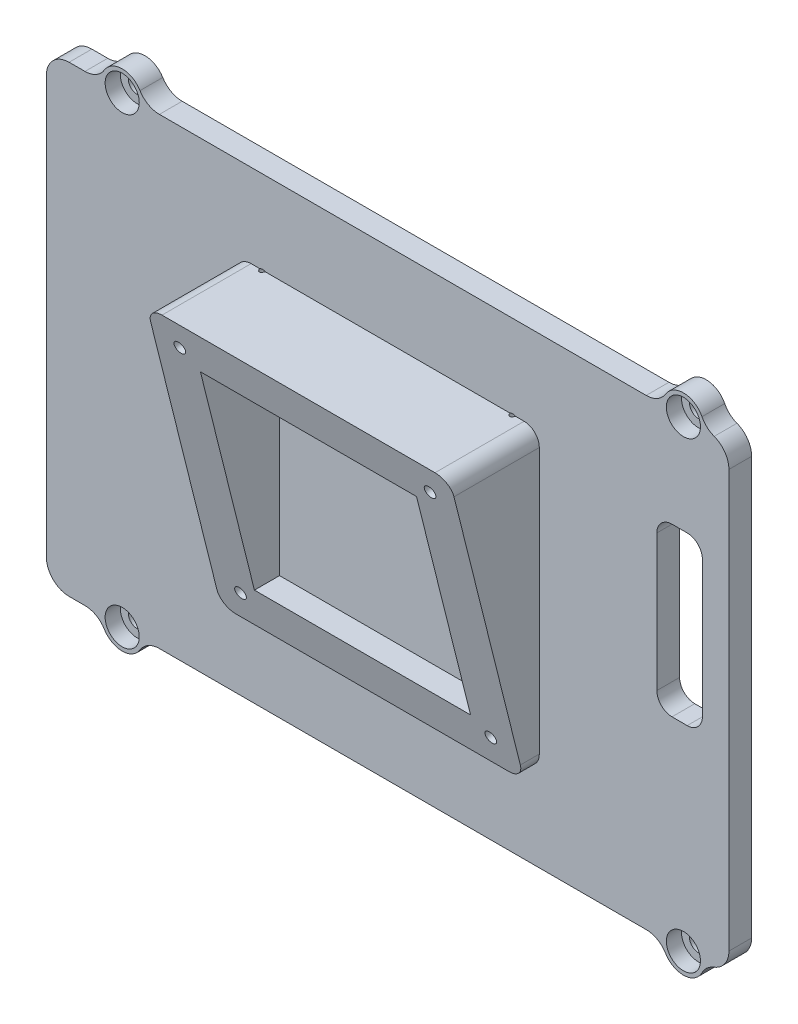
SolidWorks part; units mm, degrees
ref_plane "Спереди" through (0, 0, 0) normal (0, 0, 1) x (1, 0, 0)
ref_plane "Сверху" through (0, 0, 0) normal (0, 1, 0) x (1, 0, 0)
ref_plane "Справа" through (0, 0, 0) normal (1, 0, 0) x (0, 0, -1)
sketch "Эскиз1" plane through (0, 0, 0) normal (0, 1, 0) x (1, 0, 0)
  line L0 (0, 45) -> (0, -45) construction
  line L1 (-30.5, 45) -> (30.5, 45)
  line L2 (-30.5, 45) -> (-30.5, -45)
  line L3 (-30.5, -45) -> (30.5, -45)
  line L4 (30.5, 45) -> (30.5, -45)
  line L6 (-30.5, 0) -> (30.5, 0) construction
  point P8 (0, 0)
  dimension "D1" = 90
  dimension "D2" = 61
extrude "боковые стенки" [suppressed] add sketch "Эскиз1" along normal blind 18
sketch "Эскиз7" plane through (0, 0, 0) normal (0, 1, 0) x (1, 0, 0)
  line L1 (-30.5, 45) -> (30.5, 45)
  line L2 (-30.5, 45) -> (-30.5, -45)
  line L3 (-30.5, -45) -> (30.5, -45)
  line L4 (30.5, 45) -> (30.5, -45)
extrude "крышка" [suppressed] add sketch "Эскиз7" along normal blind 12
dome "Купол6" [suppressed] faces to dome 1 distance 10 parameters "D1"=10
shell "Оболочка1" [suppressed] thickness 2
sketch "Эскиз11" [suppressed] plane through (-30.5, 0, 0) normal (-1, 0, 0) x (0, 0, 1)
  line L1 (-45, 30) -> (45, 30) construction
  line L2 (0, 30) -> (45, 30)
  line L4 (45, 30) -> (45, 18)
  ellipse E0 centre (0, 18) end of major axis (-45, 18) minor radius 12 (45, 18) -> (0, 30) ccw
  dimension "D1" = 12
extrude "скругление вдоль" [suppressed] cut sketch "Эскиз11" against normal through all
sketch "Эскиз12" [suppressed] plane through (0, 0, -45) normal (0, 0, -1) x (-1, 0, 0)
  line L0 (-30.5, 30) -> (-30.5, 0) construction
  line L1 (-30.5, 18) -> (-30.5, 30)
  line L2 (-30.5, 30) -> (30.5, 30) construction
  line L3 (-30.5, 30) -> (0, 30)
  ellipse E0 centre (0, 18) end of major axis (-30.5, 18) minor radius 12 (0, 30) -> (-30.5, 18) ccw
  dimension "D1" = 12
extrude "скругление поперек" [suppressed] cut sketch "Эскиз12" against normal through all
mirror "Зеркальное отражение3" [suppressed] about plane through (0, 0, 0) normal (0, 0, 1)
mirror "Зеркальное отражение4" [suppressed] about plane through (0, 0, 0) normal (1, 0, 0)
shell "Оболочка5" [suppressed] thickness 2.1
sketch "Эскиз13" [suppressed] plane through (30.5, 0, 0) normal (1, 0, 0) x (0, 0, -1)
  line L0 (-45, 30) -> (-45, 0) construction
  line L1 (-36.15, 1) -> (-27.65, 1)
  line L2 (-36.15, 1) -> (-36.15, 0)
  line L3 (-36.15, 0) -> (-27.65, 0)
  line L4 (-27.65, 1) -> (-27.65, 0)
  line L5 (-45, 0) -> (45, 0) construction
  dimension "D1" = 8.5
  dimension "D3" = 8.85
  dimension "D4" = 1
extrude "отверстие для microusb" [suppressed] cut sketch "Эскиз13" against normal up to surface (2.1 mm away)
sketch "Эскиз14" [suppressed] plane through (30.5, 0, 0) normal (1, 0, 0) x (0, 0, -1)
  line L0 (-45, 30) -> (-45, 0) construction
  line L1 (-18.5, 4.5) -> (-2.5, 4.5)
  line L2 (-18.5, 4.5) -> (-18.5, 0)
  line L3 (-18.5, 0) -> (-2.5, 0)
  line L4 (-2.5, 4.5) -> (-2.5, 0)
  line L5 (-45, 0) -> (-36.15, 0) construction
  line L6 (-27.65, 0) -> (45, 0) construction
  dimension "D1" = 16
  dimension "D3" = 26.5
  dimension "D4" = 4.5
extrude "отверстие для hdmi" [suppressed] cut sketch "Эскиз14" against normal up to surface (2.1 mm away)
sketch "Эскиз15" [suppressed] plane through (30.5, 0, 0) normal (1, 0, 0) x (0, 0, -1)
  line L0 (-45, 30) -> (-45, 0) construction
  line L1 (-2.5, 0) -> (45, 0) construction
  circle A0 centre (11, 0.1) radius 3.5
  dimension "D1" = 7
  dimension "D2" = 56
  dimension "D3" = 0.1
extrude "отверстие для audio" [suppressed] cut sketch "Эскиз15" against normal up to surface (2.1 mm away)
sketch "Эскиз16" [suppressed] plane through (0, 0, -45) normal (0, 0, -1) x (-1, 0, 0)
  line L0 (-30.5, 0) -> (30.5, 0) construction
  line L1 (-26.5, 0) -> (-9, 0)
  line L2 (-26.5, 0) -> (-26.5, 11.5)
  line L3 (-26.5, 11.5) -> (-9, 11.5)
  line L4 (-9, 0) -> (-9, 11.5)
  line L5 (-30.5, 30) -> (-30.5, 0) construction
  dimension "D1" = 4
  dimension "D2" = 11.5
  dimension "D3" = 17.5
extrude "отверстие для ethernet" [suppressed] cut sketch "Эскиз16" against normal up to surface (2.1 mm away)
sketch "Эскиз17" [suppressed] plane through (0, 0, -45) normal (0, 0, -1) x (-1, 0, 0)
  line L0 (-9, 0) -> (30.5, 0) construction
  line L1 (-9, 14) -> (26.75, 14)
  line L2 (-9, 14) -> (-9, 0)
  line L3 (-9, 0) -> (26.75, 0)
  line L4 (26.75, 14) -> (26.75, 0)
  dimension "D2" = 35.75
  dimension "D3" = 14
extrude "отверстие для usb" [suppressed] cut sketch "Эскиз17" against normal up to surface (2.1 mm away)
sketch "Эскиз21" [suppressed] plane through (0, 0, 0) normal (0, 1, 0) x (1, 0, 0)
  line L0 (6.5, 0.5) -> (25.5, 0.5)
  line L1 (6.5, 3.5) -> (25.5, 3.5)
  line L3 (-30.5, -45) -> (30.5, -45) construction
  arc A0 (6.5, 3.5) -> (6.5, 0.5) centre (6.5, 2) ccw
  arc A1 (25.5, 0.5) -> (25.5, 3.5) centre (25.5, 2) ccw
  point P1 (5, 2)
  point P3 (27, 2)
  dimension "D1" = 3
  dimension "D2" = 22
  dimension "D3" = 5
  dimension "D4" = 47
extrude "отверстие для шлейфа камеры" [suppressed] cut sketch "Эскиз21" along normal through all
fillet "Скругление2" [suppressed] radius 1.5
sketch "Эскиз23" [suppressed] plane through (0, 0, 0) normal (0, -1, 0) x (1, 0, 0)
  line L0 (-33, 27) -> (-30.5, 27)
  line L1 (-33, 23) -> (0, 23) construction
  line L2 (-33, 23) -> (-33, 0) construction
  line L3 (-33, 0) -> (0, 0) construction
  line L4 (0, 23) -> (0, 0) construction
  line L5 (-30.5, -43.5) -> (-30.5, 43.5) construction
  line L6 (-30.5, 27) -> (-30.5, 19)
  line L7 (-30.5, 19) -> (-33, 19)
  line L8 (-30.5, -19) -> (-33, -19)
  line L9 (-30.5, -27) -> (-30.5, -19)
  line L10 (-33, -27) -> (-30.5, -27)
  line L11 (33, -27) -> (30.5, -27)
  line L12 (30.5, -27) -> (30.5, -19)
  line L13 (30.5, -19) -> (33, -19)
  line L14 (30.5, 36.15) -> (33, 36.15)
  line L15 (30.5, 43.5) -> (30.5, 36.15)
  line L16 (33, 43.5) -> (30.5, 43.5)
  line L17 (28.4, 36.15) -> (30.5, 36.15) construction
  line L18 (30.5, 45) -> (30.5, 36.15) construction
  circle A0 centre (-33, 23) radius 1.65
  arc A1 (-33, 27) -> (-33, 19) centre (-33, 23) ccw
  arc A2 (-33, -27) -> (-33, -19) centre (-33, -23) cw
  circle A3 centre (-33, -23) radius 1.65
  circle A4 centre (33, -23) radius 1.65
  arc A5 (33, -27) -> (33, -19) centre (33, -23) ccw
  arc A6 (33, 43.5) -> (33, 36.15) centre (33, 39.825) cw
  circle A7 centre (33, 39.825) radius 1.65
  dimension "D3" = 3.3
  dimension "D4" = 8
  dimension "D1" = 33
  dimension "D2" = 23
extrude "крепление к корпусу" [suppressed] add sketch "Эскиз23" against normal blind 5
sketch "Эскиз25" [suppressed] plane through (30.5, 0, 0) normal (1, 0, 0) x (0, 0, -1)
  line L0 (-43.5, 18) -> (43.5, 18) construction
  line L1 (-34.5, 18) -> (15.5, 18)
  line L2 (-34.5, 18) -> (-34.5, 0)
  line L3 (-34.5, 0) -> (15.5, 0)
  line L4 (15.5, 18) -> (15.5, 0)
  line L5 (-43.5, 18) -> (-43.5, 5) construction
  line L6 (42.9, 0) -> (-42.9, 0) construction
  dimension "D1" = 9
  dimension "D2" = 50
extrude "Вырез под Г-образные выводы" [suppressed] cut sketch "Эскиз25" against normal up to next
ref_plane "Плоскость1" [suppressed] through (0, 30, 0) normal (0, 1, 0) x (1, 0, 0)
sketch "Эскиз27" [suppressed] plane through (0, 30, 0) normal (0, 1, 0) x (1, 0, 0)
  line L1 (-2.77, -37) -> (19.73, -37)
  line L2 (-2.77, -37) -> (-2.77, -45)
  line L3 (-2.77, -45) -> (19.73, -45)
  line L4 (19.73, -37) -> (19.73, -45)
  line L6 (30.5, -43.5) -> (30.5, -36.15) construction
  line L7 (29, -45) -> (-29, -45) construction
  dimension "D1" = 8
  dimension "D2" = 22.5
  dimension "D3" = 10.77
extrude "Вырез под клемники (подвод питания для серв и шилда)" [suppressed] cut sketch "Эскиз27" against normal up to next
sketch "Эскиз29" plane through (0, 0, 0) normal (0, 0, 1) x (1, 0, 0)
  line L1 (-45, 30.5) -> (45, 30.5)
  line L2 (-45, 30.5) -> (-45, -30.5)
  line L3 (-45, -30.5) -> (45, -30.5)
  line L4 (45, 30.5) -> (45, -30.5)
  point P5 (0, -30.5)
  point P7 (45, 0)
  dimension "D1" = 90
  dimension "D2" = 61
extrude "Основа крышки" add sketch "Эскиз29" along normal mid plane 3
sketch "Эскиз30" plane through (0, 0, 1.5) normal (0, 0, 1) x (1, 0, 0)
  line L5 (45, -30.5) -> (45, 30.5) construction
  line L6 (35.5, 17.5) -> (41.5, 17.5)
  line L7 (35.5, 17.5) -> (35.5, -4.5)
  line L8 (35.5, -4.5) -> (41.5, -4.5)
  line L9 (41.5, 17.5) -> (41.5, -4.5)
  line L10 (45, 30.5) -> (-45, 30.5) construction
  dimension "D1" = 22
  dimension "D2" = 6
  dimension "D3" = 3.5
  dimension "D4" = 13
extrude "Под винты клеммника" cut sketch "Эскиз30" against normal up to next
sketch "Эскиз31" plane through (0, 0, 1.5) normal (0, 0, 1) x (1, 0, 0)
  line L1 (-12.75, 25.5) -> (8.75, 25.5)
  line L2 (-12.75, 25.5) -> (-12.75, 21.5)
  line L3 (-12.75, 21.5) -> (8.75, 21.5)
  line L4 (8.75, 25.5) -> (8.75, 21.5)
  line L5 (45, 30.5) -> (-45, 30.5) construction
  line L6 (-45, 30.5) -> (-45, -30.5) construction
  point P4 (-2, 25.5)
  dimension "D1" = 21.5
  dimension "D2" = 43
  dimension "D3" = 4
  dimension "D4" = 5
extrude "Под шлейф камеры" [suppressed] cut sketch "Эскиз31" against normal through all
sketch "Эскиз32" plane through (0, 0, 1.5) normal (0, 0, 1) x (1, 0, 0)
  line L1 (45, 30.5) -> (-45, 30.5) construction
  line L2 (45, -30.5) -> (45, 30.5) construction
  circle A0 centre (2, 0.5) radius 3
  dimension "D1" = 6
  dimension "D2" = 30
  dimension "D3" = 43
extrude "Под кнопку RESET" [suppressed] cut sketch "Эскиз32" against normal through all
fillet "Скругление3" radius 3 4 edges at (-45, -30.5, 0) (-45, 30.5, 0) (45, 30.5, 0) (45, -30.5, 0)
sketch "Эскиз33" plane through (0, 0, 1.5) normal (0, 0, 1) x (1, 0, 0)
  line L0 (-45, 0) -> (0, 0) construction
  line L1 (-45, 27.5) -> (-45, -27.5) construction
  line L2 (0, 0) -> (0, -30.5) construction
  line L3 (-42, -30.5) -> (42, -30.5) construction
  line L4 (-37.75, -30.5) -> (-32.25, -30.5)
  line L5 (-37.75, 30.5) -> (-32.25, 30.5)
  line L6 (41.75, -30.5) -> (36.25, -30.5)
  line L7 (45, -27.5) -> (45, 27.5) construction
  line L11 (36.25, 30.5) -> (41.75, 30.5)
  line L13 (42, 30.5) -> (-42, 30.5) construction
  arc A0 (-37.75, -30.5) -> (-32.25, -30.5) centre (-35, -30.5) ccw
  arc A1 (-37.75, 30.5) -> (-32.25, 30.5) centre (-35, 30.5) cw
  arc A2 (41.75, -30.5) -> (36.25, -30.5) centre (39, -30.5) cw
  arc A4 (36.25, 30.5) -> (41.75, 30.5) centre (39, 30.5) cw
  point P33 (39, 30.5)
  point P35 (39, -30.5)
  dimension "D1" = 2.75
  dimension "D3" = 6
  dimension "D2" = 10
extrude "Наплывы под шурупы для крепления с корпусом" add sketch "Эскиз33" against normal up to surface (3 mm away) up to face at (38.5, 6.5, -1.5)
sketch "Эскиз34" plane through (0, 0, 1.5) normal (0, 0, 1) x (1, 0, 0)
  circle A0 centre (-35, -30.5) radius 1.2
  circle A1 centre (39, -30.5) radius 1.2
  circle A3 centre (-35, 30.5) radius 1.2
  circle A4 centre (39, 30.5) radius 1.2
  arc A7 (41.75, 30.5) -> (36.25, 30.5) centre (39, 30.5) ccw construction
  dimension "D1" = 2.4
extrude "Отверстия под шурупы для крепления с корпусом" cut sketch "Эскиз34" against normal up to next
sketch "Эскиз35" plane through (0, 0, 1.5) normal (0, 0, 1) x (1, 0, 0)
  circle A0 centre (-35, -30.5) radius 2.25
  circle A1 centre (-35, 30.5) radius 2.25
  circle A3 centre (39, -30.5) radius 2.25
  circle A5 centre (39, 30.5) radius 2.25
  dimension "D1" = 4.5
extrude "Углубления под шляпки" cut sketch "Эскиз35" against normal blind 2
fillet "Скругление под шлейф" [suppressed] radius 2
fillet "Скругление5" radius 2 4 edges at (35.5, -4.5, 0) (41.5, -4.5, 0) (41.5, 17.5, 0) (35.5, 17.5, 0)
sketch "Эскиз36" plane through (0, 0, 1.5) normal (0, 0, 1) x (1, 0, 0)
  line L1 (-20, 19.5) -> (20, 19.5)
  line L2 (-20, 19.5) -> (-20, -19.5)
  line L3 (-20, -19.5) -> (20, -19.5)
  line L4 (20, 19.5) -> (20, -19.5)
  line L5 (-14.25, 14.25) -> (14.25, 14.25)
  line L6 (-14.25, 14.25) -> (-14.25, -14.25)
  line L7 (-14.25, -14.25) -> (14.25, -14.25)
  line L8 (14.25, 14.25) -> (14.25, -14.25)
  point P8 (0, 14.25)
  point P9 (0, 19.5)
  point P10 (0, -19.5)
  point P11 (20, 0)
  point P12 (-14.25, 0)
  point P13 (-20, 0)
  dimension "D1" = 39
  dimension "D2" = 40
  dimension "D3" = 28.5
extrude "Выступ для крепления дисплея" add sketch "Эскиз36" along normal blind 12
chamfer "Фаска2" distance 10 distance2 40 1 edges at (0, -19.5, 13.5) first distance on face at (0, -19.5, 7.5)
sketch "Эскиз37" plane through (0, -1.9706, 7.8824) normal (0, -0.2425, 0.9701) x (1, 0, 0)
  line L0 (-16.5, 18.6314) -> (16.5, -14.3686) construction
  line L1 (-16.5, 18.6314) -> (16.5, 18.6314) construction
  line L2 (-16.5, 18.6314) -> (-16.5, -14.3686) construction
  line L3 (-16.5, -14.3686) -> (16.5, -14.3686) construction
  line L4 (16.5, 18.6314) -> (16.5, -14.3686) construction
  line L5 (-16.5, -14.3686) -> (16.5, 18.6314) construction
  line L10 (20, -18.0689) -> (-20, -18.0689) construction
  line L12 (20, 22.1314) -> (-20, 22.1314) construction
  circle A0 centre (-16.5, 18.6314) radius 0.75
  circle A1 centre (16.5, 18.6314) radius 0.75
  circle A2 centre (16.5, -14.3686) radius 0.75
  circle A3 centre (-16.5, -14.3686) radius 0.75
  point P12 (0, -14.3686)
  point P13 (0, 2.1314)
  point P23 (0, 2.1314)
  point P25 (0, -18.0689)
  dimension "D1" = 1.5
  dimension "D2" = 33
  dimension "D4" = 3.5
  dimension "D3" = 4
extrude "Отверстия для креплени дисплея в корпусе" cut sketch "Эскиз37" against normal offset from surface (13.1107 mm away) 1 up to face at (40.2, -30.5, -1.5)
sketch "Эскиз38" plane through (0, 0, 1.5) normal (0, 0, 1) x (1, 0, 0)
  line L0 (14.25, 14.25) -> (-14.25, 14.25) construction
  line L1 (-7.5, 14.25) -> (7.5, 14.25)
  line L2 (-7.5, 14.25) -> (-7.5, 6.25)
  line L3 (-7.5, 6.25) -> (7.5, 6.25)
  line L4 (7.5, 14.25) -> (7.5, 6.25)
  point P4 (0, 14.25)
  point P7 (0, 14.25)
  dimension "D1" = 8
  dimension "D2" = 15
extrude "Под провод дисплея" cut sketch "Эскиз38" against normal up to next
fillet "Скругление6" radius 2 4 edges at (7.5, 6.25, 0) (7.5, 14.25, 0) (-7.5, 14.25, 0) (-7.5, 6.25, 0)
fillet "Скругление7" radius 2 4 edges at (-20, -19.5, 2.5) (20, -19.5, 2.5) (20, 19.5, 7.375) (-20, 19.5, 7.375)
fillet "Скругление8" radius 3 8 edges at (-37.75, 30.5, 0) (-32.25, 30.5, 0) (36.25, -30.5, 0) (41.75, -30.5, 0) (-32.25, -30.5, 0) (-37.75, -30.5, 0) (36.25, 30.5, 0) (41.75, 30.5, 0)
